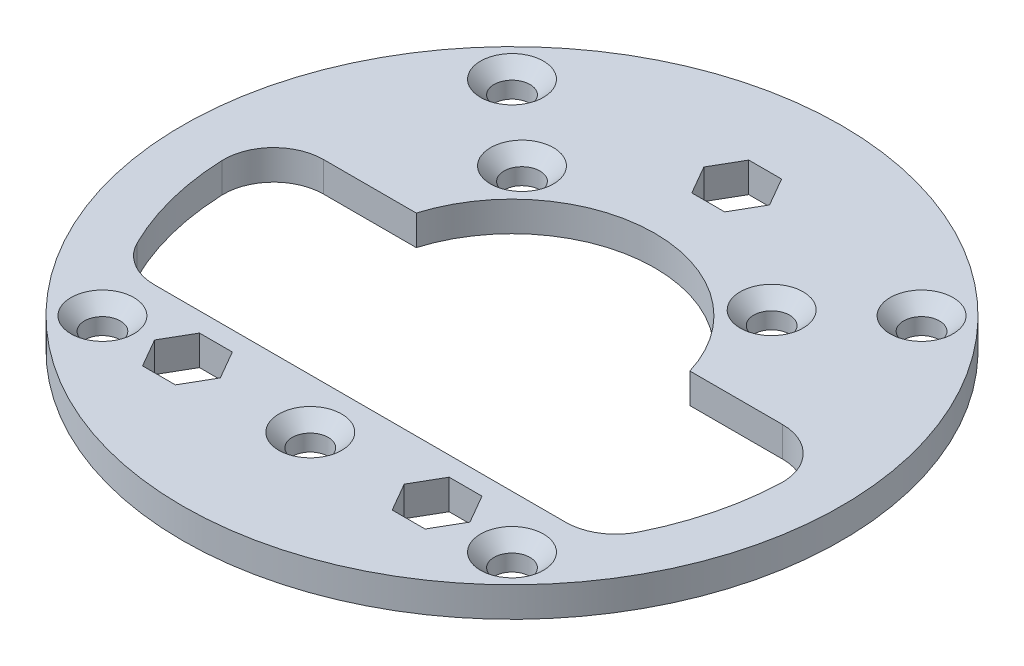
SolidWorks part; units mm, degrees
material "PEI"
ref_plane "Front Plane" through (0, 0, 0) normal (0, 0, 1) x (1, 0, 0)
ref_plane "Top Plane" through (0, 0, 0) normal (0, 1, 0) x (1, 0, 0)
ref_plane "Right Plane" through (0, 0, 0) normal (1, 0, 0) x (0, 0, -1)
sketch "Sketch1" plane through (0, 0, 0) normal (0, 1, 0) x (1, 0, 0)
  circle A0 centre (0, 0) radius 33
  circle A1 centre (0, 0) radius 28
  dimension "D1" = 66
  dimension "D2" = 5
extrude "Boss-Extrude1" add sketch "Sketch1" along normal blind 3
sketch "Sketch2" plane through (0, 3, 0) normal (0, 1, 0) x (1, 0, 0)
  line L0 (-23.5, -15.2233) -> (23.5, -15.2233)
  line L1 (-27.6968, 4.1095) -> (-13.6968, 4.1095)
  line L2 (0, 0) -> (7.7557, 0) construction
  line L3 (13.6968, 4.1095) -> (27.6968, 4.1095)
  line L4 (-20.5061, 20.5061) -> (0, 0) construction
  line L5 (-12.5, 13.5) -> (12.5, 13.5) construction
  circle A0 centre (0, 22.5) radius 2.25 construction
  circle A1 centre (-12.5, -20) radius 2.25 construction
  circle A2 centre (12.5, -20) radius 2.25 construction
  circle A4 centre (-12.5, 13.5) radius 1.5
  circle A6 centre (0, 0) radius 28 construction
  arc A8 (-13.6968, 4.1095) -> (13.6968, 4.1095) centre (0, 0) cw
  arc A9 (27.6968, 4.1095) -> (-27.6968, 4.1095) centre (0, 0) ccw
  arc A10 (23.5, -15.2233) -> (-23.5, -15.2233) centre (0, 0) cw
  circle A11 centre (12.5, 13.5) radius 1.5
  circle A12 centre (0, 0) radius 29 construction
  circle A13 centre (0, 0) radius 33 construction
  circle A14 centre (-20.5061, 20.5061) radius 1.75 construction
  circle A15 centre (20.5061, 20.5061) radius 1.75 construction
  circle A16 centre (20.5061, -20.5061) radius 1.75 construction
  circle A17 centre (-20.5061, -20.5061) radius 1.75 construction
  circle A18 centre (0, -20.2) radius 1.5
  point P15 (0, 13.5)
  point P19 (0, 0)
  point P44 (0, 0)
  circle M2 centre (0, 0) radius 28
  dimension "D5" = 4.5
  dimension "D6" = 4.5
  dimension "D7" = 4.5
  dimension "D12" = 14.3
  dimension "D16" = 3.5
  dimension "D11" = 3
  dimension "D1" = 25
  dimension "D2" = 12.5
  dimension "D3" = 22.5
  dimension "D4" = 20
  dimension "D14" = 4
  dimension "D15" = 135
  dimension "D8" = 14
  dimension "D9" = 14
  dimension "D10" = 47
  dimension "D18" = 25
  dimension "D19" = 20.2
  dimension "D13" = 13.5
  dimension "D17" = 4
extrude "Saliente-Extruir1" add sketch "Sketch2" against normal up to surface (3 mm away) contours L1 A8 L3 M2 | L0 M2 region at (0, 3, 15.7104) region at (0, 3, -15.6634) up to face at (0, 0, 33)
sketch "Croquis1" plane through (0, 3, 0) normal (0, 1, 0) x (1, 0, 0)
  line L1 (-9.2091, -20) -> (-10.8546, -17.15)
  line L2 (-10.8546, -17.15) -> (-14.1454, -17.15)
  line L3 (-14.1454, -17.15) -> (-15.7909, -20)
  line L4 (-15.7909, -20) -> (-14.1454, -22.85)
  line L5 (-14.1454, -22.85) -> (-10.8546, -22.85)
  line L6 (-10.8546, -22.85) -> (-9.2091, -20)
  line L7 (15.7909, -20) -> (14.1454, -17.15)
  line L8 (14.1454, -17.15) -> (10.8546, -17.15)
  line L9 (10.8546, -17.15) -> (9.2091, -20)
  line L10 (9.2091, -20) -> (10.8546, -22.85)
  line L11 (10.8546, -22.85) -> (14.1454, -22.85)
  line L12 (14.1454, -22.85) -> (15.7909, -20)
  line L13 (3.2909, 22.5) -> (1.6454, 25.35)
  line L14 (1.6454, 25.35) -> (-1.6454, 25.35)
  line L15 (-1.6454, 25.35) -> (-3.2909, 22.5)
  line L16 (-3.2909, 22.5) -> (-1.6454, 19.65)
  line L17 (-1.6454, 19.65) -> (1.6454, 19.65)
  line L18 (1.6454, 19.65) -> (3.2909, 22.5)
  circle A0 centre (-20.5061, 20.5061) radius 1.75 construction
  circle A1 centre (-20.5061, 20.5061) radius 1.75
  circle A4 centre (20.5061, 20.5061) radius 1.75 construction
  circle A5 centre (20.5061, 20.5061) radius 1.75
  circle A6 centre (-12.5, -20) radius 2.85 construction
  circle A7 centre (12.5, -20) radius 2.85 construction
  circle A8 centre (0, 22.5) radius 2.85 construction
  circle A16 centre (-20.5061, -20.5061) radius 1.75 construction
  circle A17 centre (-20.5061, -20.5061) radius 1.75
  circle A18 centre (20.5061, -20.5061) radius 1.75 construction
  circle A19 centre (20.5061, -20.5061) radius 1.75
  dimension "D1" = 5.7
  dimension "D2" = 5.7
  dimension "D3" = 5.7
extrude "Cortar-Extruir1" cut sketch "Croquis1" against normal up to next
hole_wizard "CSK for M3 Flat Head Machine Screw1" positions "Sketch4" profile "Sketch5" countersink size "M3" standard "ANSI Metric" end condition through all
sketch "Sketch4" plane through (0, 3, 0) normal (0, 1, 0) x (1, 0, 0)
  point P0 (-20.5061, 20.5061)
  point P3 (20.5061, 20.5061)
  point P6 (20.5061, -20.5061)
  point P9 (-20.5061, -20.5061)
sketch "Sketch5" plane through (-20.5061, 3, -20.5061) normal (1, 0, 0) x (0, 0, 1)
  line L0 (0, 0) -> (0, 3)
  line L1 (0, 3) -> (1.8, 3)
  line L2 (1.8, 3) -> (1.8, 1.35)
  line L3 (1.8, 1.35) -> (3.15, 0)
  line L5 (3.15, 0) -> (0, 0)
  line L6 (-1.8, 1.35) -> (-3.15, 0) construction
  line L11 (0, -6.35) -> (0, 107.95) construction
  dimension "Thru Hole Dia." = 3.6
  dimension "Thru Hole Depth" = 3
  dimension "Near C'Sink Dia." = 6.3
  dimension "Near C'Sink Angle" = 90
hole_wizard "CSK for M3 Flat Head Machine Screw2" positions "Sketch6" profile "Sketch7" countersink size "M3" standard "ANSI Metric" end condition through all
sketch "Sketch6" plane through (0, 3, 0) normal (0, 1, 0) x (1, 0, 0)
  point P12 (-12.5, 13.5)
  point P15 (12.5, 13.5)
  point P18 (0, -20.2)
sketch "Sketch7" plane through (-12.5, 3, -13.5) normal (1, 0, 0) x (0, 0, 1)
  line L0 (0, 0) -> (0, 3)
  line L1 (0, 3) -> (1.8, 3)
  line L2 (1.8, 3) -> (1.8, 1.35)
  line L3 (1.8, 1.35) -> (3.15, 0)
  line L5 (3.15, 0) -> (0, 0)
  line L6 (-1.8, 1.35) -> (-3.15, 0) construction
  line L11 (0, -6.35) -> (0, 107.95) construction
  dimension "Thru Hole Dia." = 3.6
  dimension "Thru Hole Depth" = 3
  dimension "Near C'Sink Dia." = 6.3
  dimension "Near C'Sink Angle" = 90
fillet "Fillet1" radius 5 4 edges at (-27.6968, 1.5, -4.1095) (27.6968, 1.5, -4.1095) (23.5, 1.5, 15.2233) (-23.5, 1.5, 15.2233)
equation "\"D2@Sketch2\"=\"D1@Sketch2\"/2"
equation "\"D6@Sketch2\"=\"D5@Sketch2\""
equation "\"D7@Sketch2\"=\"D6@Sketch2\""
